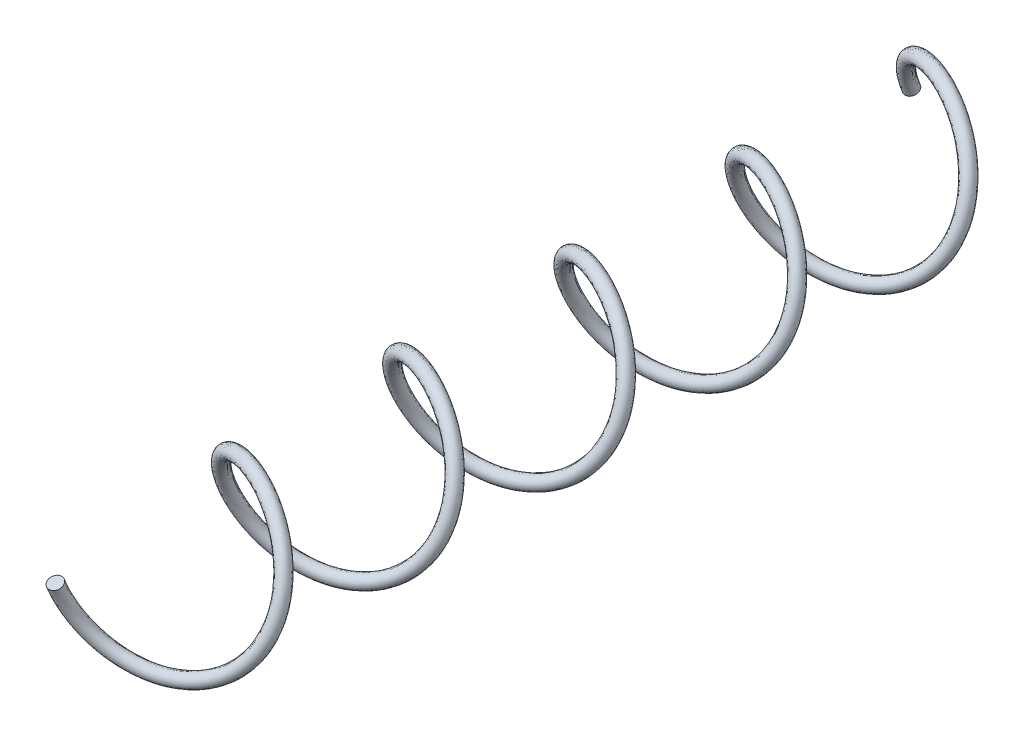
SolidWorks part; units mm, degrees
note: '?' marks a value the reader was unsure of.
ref_plane "Plan de face" through (0, 0, 0) normal (0, 0, 1) x (1, 0, 0)
ref_plane "Plan de dessus" through (0, 0, 0) normal (0, 1, 0) x (1, 0, 0)
ref_plane "Plan de droite" through (0, 0, 0) normal (1, 0, 0) x (0, 0, -1)
sketch "Esquisse1" plane through (0, 0, 0) normal (0, 0, 1) x (1, 0, 0)
  circle A0 centre (0, 0) radius 20
  point P3 (0, 0)
  point P4 (0, 0)
  dimension "D1" = 40
curve "Hélice/Spirale1" pitch 50 height 250 turns 5
sweep "Balayage1" add path "Hélice/Spirale1" circular profile diameter 4 parameters "D3"=4
ref_axis "Axe1" through (0, 0, 0) along (0, 0, 1)?
